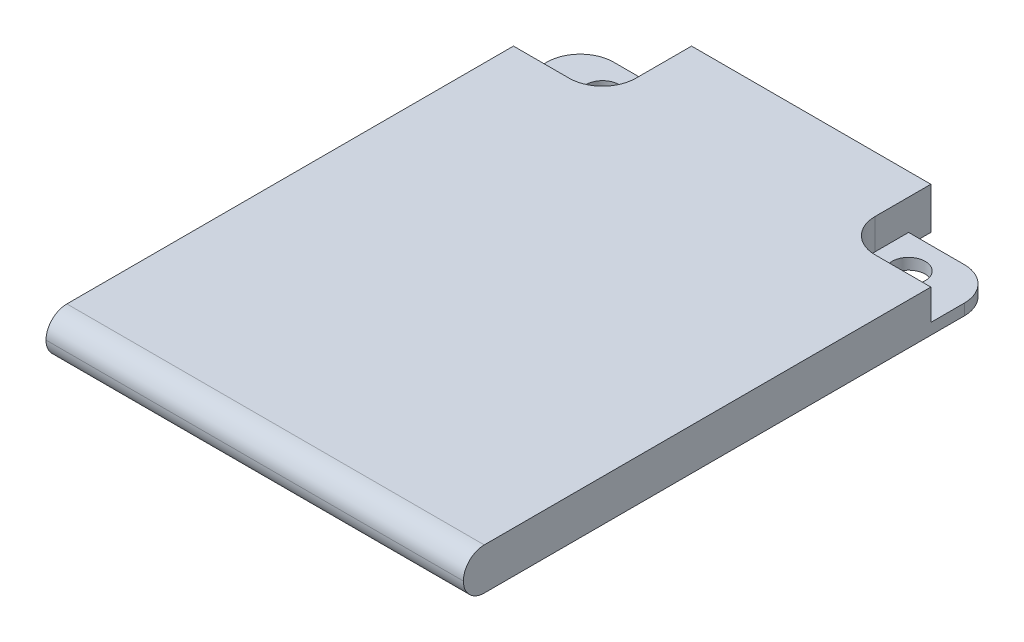
SolidWorks part; units mm, degrees
ref_plane "Front Plane" through (0, 0, 0) normal (0, 0, 1) x (1, 0, 0)
ref_plane "Top Plane" through (0, 0, 0) normal (0, 1, 0) x (1, 0, 0)
ref_plane "Right Plane" through (0, 0, 0) normal (1, 0, 0) x (0, 0, -1)
sketch "Sketch1" plane through (0, 0, 0) normal (0, 1, 0) x (1, 0, 0)
  line L0 (0, 0) -> (37.5, 0)
  line L1 (37.5, 0) -> (37.5, 48)
  line L2 (37.5, 48) -> (29.5, 48)
  line L3 (29.5, 48) -> (29.5, 50)
  line L4 (29.5, 50) -> (8, 50)
  line L5 (8, 50) -> (8, 48)
  line L6 (8, 48) -> (0, 48)
  line L7 (0, 48) -> (0, 0)
  circle A0 centre (5, 45) radius 1.5
  circle A1 centre (32.5, 45) radius 1.5
  dimension "D3" = 3
  dimension "D1" = 50
  dimension "D2" = 8
  dimension "D4" = 3
  dimension "D5" = 2
  dimension "D6" = 5
  dimension "D7" = 5
  dimension "D8" = 37.5
extrude "Boss-Extrude1" add sketch "Sketch1" along normal blind 3.75
fillet "Fillet1" radius 1.875 2 edges at (18.75, 0, 0) (18.75, 3.75, 0)
sketch "Sketch2" plane through (0, 3.75, 0) normal (0, 1, 0) x (1, 0, 0)
  line L0 (0, 48) -> (0, 1.875) construction
  line L1 (8, 48) -> (0, 48)
  line L2 (8, 48) -> (8, 45)
  line L3 (5, 42) -> (0, 42)
  line L4 (0, 48) -> (0, 42)
  line L5 (37.5, 1.875) -> (37.5, 48) construction
  line L6 (29.5, 48) -> (37.5, 48)
  line L7 (29.5, 48) -> (29.5, 45)
  line L8 (32.5, 42) -> (37.5, 42)
  line L9 (37.5, 48) -> (37.5, 42)
  arc A0 (29.5, 45) -> (32.5, 42) centre (32.5, 45) ccw
  arc A1 (8, 45) -> (5, 42) centre (5, 45) cw
  dimension "D2" = 3
  dimension "D1" = 6
extrude "Cut-Extrude1" cut sketch "Sketch2" against normal blind 2.75
fillet "Fillet2" radius 3 2 edges at (37.5, 0.5, -48) (0, 0.5, -48)
